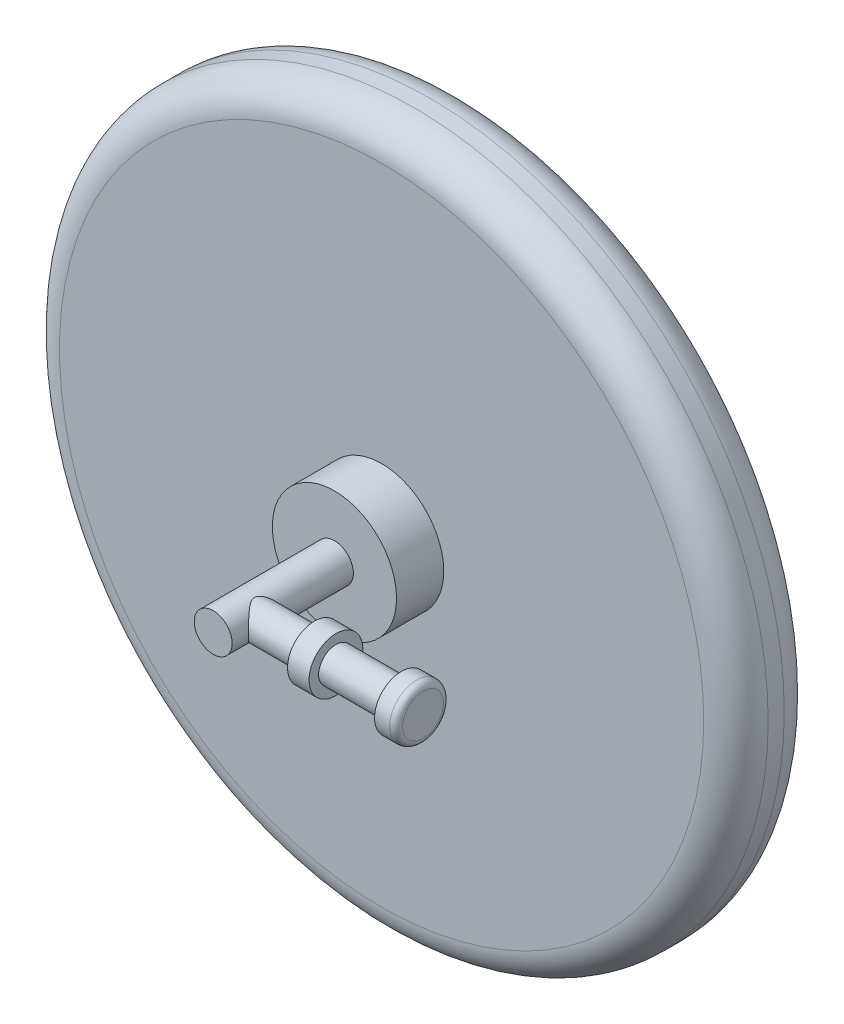
SolidWorks part; units mm, degrees
ref_plane "Front Plane" through (0, 0, 0) normal (0, 0, 1) x (1, 0, 0)
ref_plane "Top Plane" through (0, 0, 0) normal (0, 1, 0) x (1, 0, 0)
ref_plane "Right Plane" through (0, 0, 0) normal (1, 0, 0) x (0, 0, -1)
ref_plane "Plane1"
sketch "Sketch1" plane through (0, 0, 0) normal (0, 0, 1) x (1, 0, 0)
  circle A0 centre (0, 0) radius 279.4
extrude "Extrusion1" add sketch "Sketch1" along normal blind 25.4 and the other way blind 38.1
fillet "Fillet1" radius 25.4 2 edges at (279.4, 0, -38.1) (279.4, 0, 25.4)
sketch "Sketch2" plane through (0, 0, 25.4) normal (0, 0, 1) x (1, 0, 0)
  circle A0 centre (0, 0) radius 48.9585
  dimension "D1" = 97.917
extrude "Extrusion2" add sketch "Sketch2" along normal blind 37.211
sketch "Sketch3" plane through (0, 0, 62.611) normal (0, 0, 1) x (1, 0, 0)
  circle A0 centre (0, 0) radius 14.9225
  dimension "D1" = 29.845
extrude "Extrusion3" add sketch "Sketch3" along normal blind 95.6056
ref_plane "Plane2"
sketch "Sketch4" plane through (0, 0, 0) normal (1, 0, 0) x (0, 1, 0)
  line L0 (14.9225, 158.2166) -> (-14.9225, 158.2166) construction
  circle A0 centre (0, 131.7371) radius 13.6525
  dimension "D1" = 27.305
  dimension "D2" = 26.4795
extrude "Extrusion4" add sketch "Sketch4" along normal blind 133.8072
sketch "Sketch5" plane through (133.8072, 0, 0) normal (1, 0, 0) x (0, 0, -1)
  circle A0 centre (-131.7371, 0) radius 21.209
  circle A1 centre (-131.7371, 0) radius 13.6525
  dimension "D1" = 42.418
extrude "Extrusion5" add sketch "Sketch5" against normal blind 80.4672
sketch "Sketch6" plane through (133.8072, 0, 0) normal (1, 0, 0) x (0, 0, -1)
  circle A0 centre (-131.7371, 0) radius 21.209
extrude "Extrusion6" cut sketch "Sketch6" against normal blind 63.5
sketch "Sketch7" plane through (70.3072, 0, 0) normal (1, 0, 0) x (0, 0, -1)
  circle A0 centre (-131.7371, 0) radius 13.6525
extrude "Extrusion7" add sketch "Sketch7" along normal blind 51.6636
sketch "Sketch8" plane through (121.9708, 0, 0) normal (1, 0, 0) x (0, 0, -1)
  circle A0 centre (-131.7371, 0) radius 21.209
extrude "Extrusion8" add sketch "Sketch8" along normal blind 17.018
fillet "Fillet2" radius 5.08 1 edges at (138.9888, 0, 110.5281)
